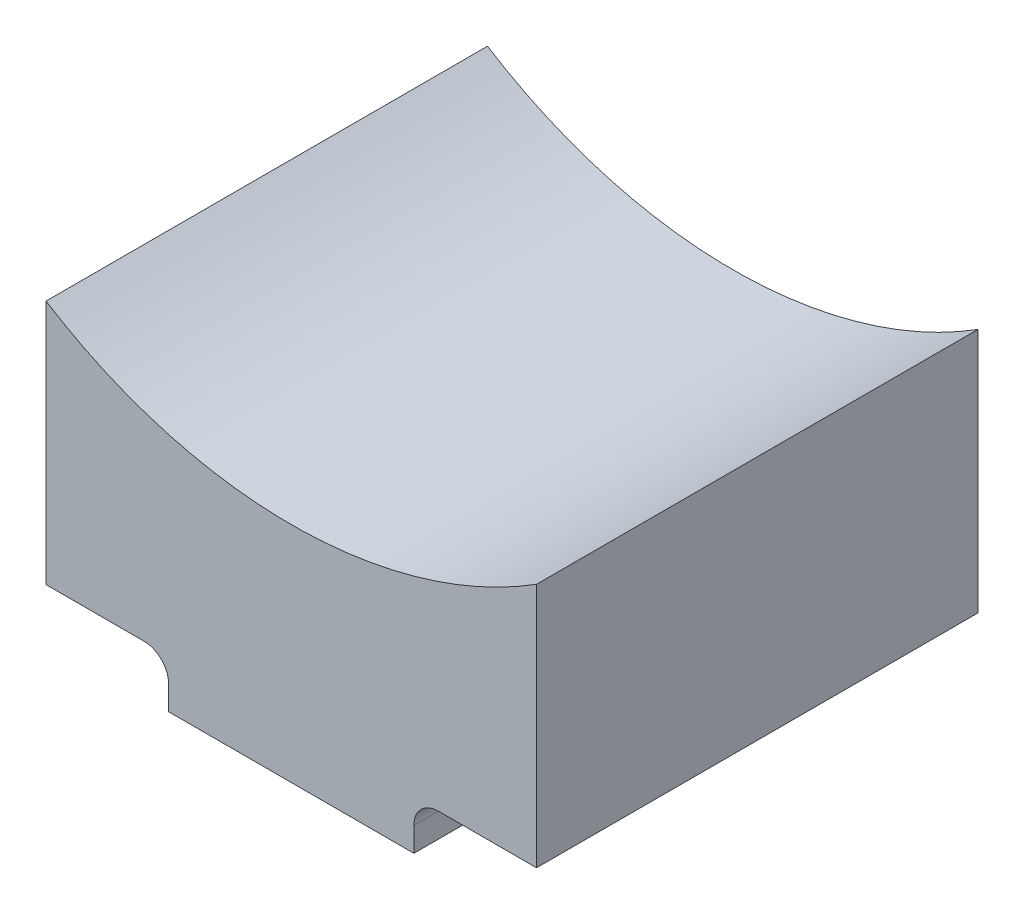
SolidWorks part; units mm, degrees
material "Ice"
ref_plane "Front Plane" through (0, 0, 0) normal (0, 0, 1) x (1, 0, 0)
ref_plane "Top Plane" through (0, 0, 0) normal (0, 1, 0) x (1, 0, 0)
ref_plane "Right Plane" through (0, 0, 0) normal (1, 0, 0) x (0, 0, -1)
sketch "Sketch1" plane through (0, 0, 0) normal (0, 0, 1) x (1, 0, 0)
  line L0 (10, 3.9928) -> (10, -6.0185)
  line L1 (-10, 3.9928) -> (-10, -6.0185)
  line L2 (-10, -6.0185) -> (-6, -6.0185)
  line L3 (10, -6.0185) -> (6, -6.0185)
  line L4 (5, -7.0185) -> (5, -8.0072)
  line L5 (0, 0) -> (0, 15264.4079) construction
  line L6 (-5, -7.0185) -> (-5, -8.0072)
  line L11 (-5, -8.0072) -> (5, -8.0072)
  arc A0 (-10, 3.9928) -> (10, 3.9928) centre (0, 19.8337) ccw
  arc A1 (5, -7.0185) -> (6, -6.0185) centre (6, -7.0185) cw
  arc A2 (-5, -7.0185) -> (-6, -6.0185) centre (-6, -7.0185) ccw
  point P13 (5, -6.0185)
  dimension "D1" = 12
  dimension "D2" = 10
  dimension "D3" = 12
extrude "Boss-Extrude1" add sketch "Sketch1" along normal mid plane 18 contours A0 L0 L3 A1 L4 L11 L6 A2 L2 L1
